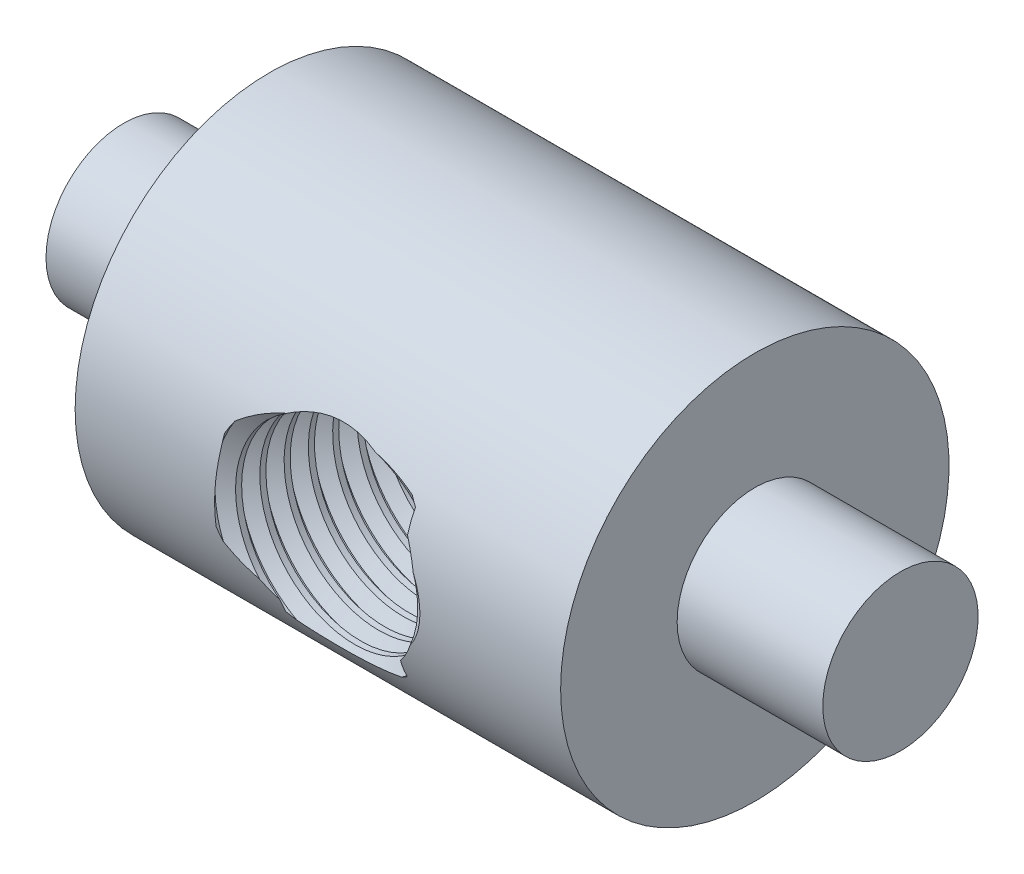
SolidWorks part; units mm, degrees
ref_plane "Front Plane" through (0, 0, 0) normal (0, 0, 1) x (1, 0, 0)
ref_plane "Top Plane" through (0, 0, 0) normal (0, 1, 0) x (1, 0, 0)
ref_plane "Right Plane" through (0, 0, 0) normal (1, 0, 0) x (0, 0, -1)
sketch "Sketch1" plane through (0, 0, 0) normal (1, 0, 0) x (0, 0, -1)
  circle A0 centre (-15.1401, 15.4224) radius 10
  dimension "D1" = 20
extrude "Main" add sketch "Sketch1" along normal blind 40
sketch "Sketch2" plane through (0, 0, 0) normal (-1, 0, 0) x (0, 0, 1)
  circle A0 centre (15.1401, 15.4224) radius 10
  circle A1 centre (15.1401, 15.4224) radius 4
  circle A2 centre (15.1401, 15.4224) radius 10 construction
  dimension "D1" = 8
extrude "Cap Remove 1" cut sketch "Sketch2" against normal blind 7.5
sketch "Sketch3" plane through (40, 0, -40) normal (-1, 0, 0) x (0, 0, 1)
  circle A0 centre (55.1401, 15.4224) radius 10
  circle A1 centre (55.1401, 15.4224) radius 4
  circle A3 centre (55.1401, 15.4224) radius 10 construction
  dimension "D1" = 8
extrude "Cap Remove 2" cut sketch "Sketch3" along normal blind 7.5
sketch "Sketch4" plane through (0, 0, 0) normal (0, 0, 1) x (1, 0, 0)
  line L0 (20, 15.4224) -> (27.7827, 15.4224) construction
  line L1 (20, 15.4224) -> (20, 23.1806) construction
  line L2 (32.5, 5.4224) -> (32.5, 25.4224) construction
  line L3 (7.5, 25.4224) -> (7.5, 5.4224) construction
  line L4 (32.5, 25.4224) -> (7.5, 25.4224) construction
  line L5 (7.5, 5.4224) -> (32.5, 5.4224) construction
  circle A0 centre (20, 15.4224) radius 5
  dimension "D1" = 10
extrude "M10Hole" cut sketch "Sketch4" along normal through all both and the other way through all
thread "Thread1" pitch 1.25 method cut profile "Thread Profile1" start angle 0, offset 0, length 30, pitch 1.25, diameter 10
ref_plane "Plane2" through (25, 15.4224, 0) normal (0, -1, 0) x (1, 0, 0)
sketch "Thread Profile1" plane through (25, 15.4224, 0) normal (0, -1, 0) x (1, 0, 0)
  line L0 (0, 0) -> (0, 1.25) construction
  line L1 (0, 0) -> (0.6766, 0.3906)
  line L2 (0.6766, 0.3906) -> (0.6766, 0.5469)
  line L3 (0.6766, 0.5469) -> (0, 0.9375)
  line L4 (0.6766, 0.4687) -> (0, 0.4687) construction
  line L11 (0, 0) -> (0, 0.9375)
  point P2 (0, 0)
  dimension "Pitch" = 1.25
  dimension "Profile_Angle" = 60
  dimension "Profile_Land" = 0.1562
  dimension "Profile_Height" = 0.6766
